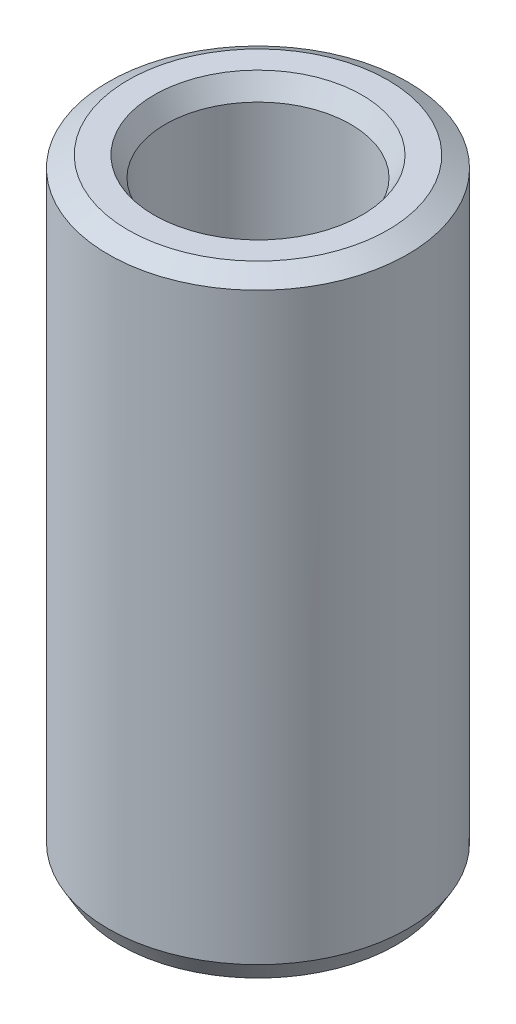
SolidWorks part; units mm, degrees
ref_plane "Front Plane" through (0, 0, 0) normal (0, 0, 1) x (1, 0, 0)
ref_plane "Top Plane" through (0, 0, 0) normal (0, 1, 0) x (1, 0, 0)
ref_plane "Right Plane" through (0, 0, 0) normal (1, 0, 0) x (0, 0, -1)
sketch "Sketch1" plane through (0, 0, 0) normal (0, 1, 0) x (1, 0, 0)
  circle A0 centre (0, 0) radius 47.5
  dimension "SLEEVE_OD" = 95
extrude "Boss-Extrude1" add sketch "Sketch1" along normal blind 195.2962
sketch "Sketch2" plane through (0, 0, 0) normal (0, 1, 0) x (1, 0, 0)
  circle A0 centre (0, 0) radius 29.4229
  dimension "BORE_D" = 58.8458
extrude "Cut-Extrude1" cut sketch "Sketch2" along normal through all
chamfer "Chamfer1" distance 3.6042 angle 60 4 edges at (0, 195.2962, 29.4229) (0, 0, 29.4229) (0, 0, 47.5) (0, 195.2962, 47.5) first distance on face at (0, 195.2962, 29.4229) first distance on face at (0, 0, 29.4229) first distance on face at (0, 195.2962, 47.5)
